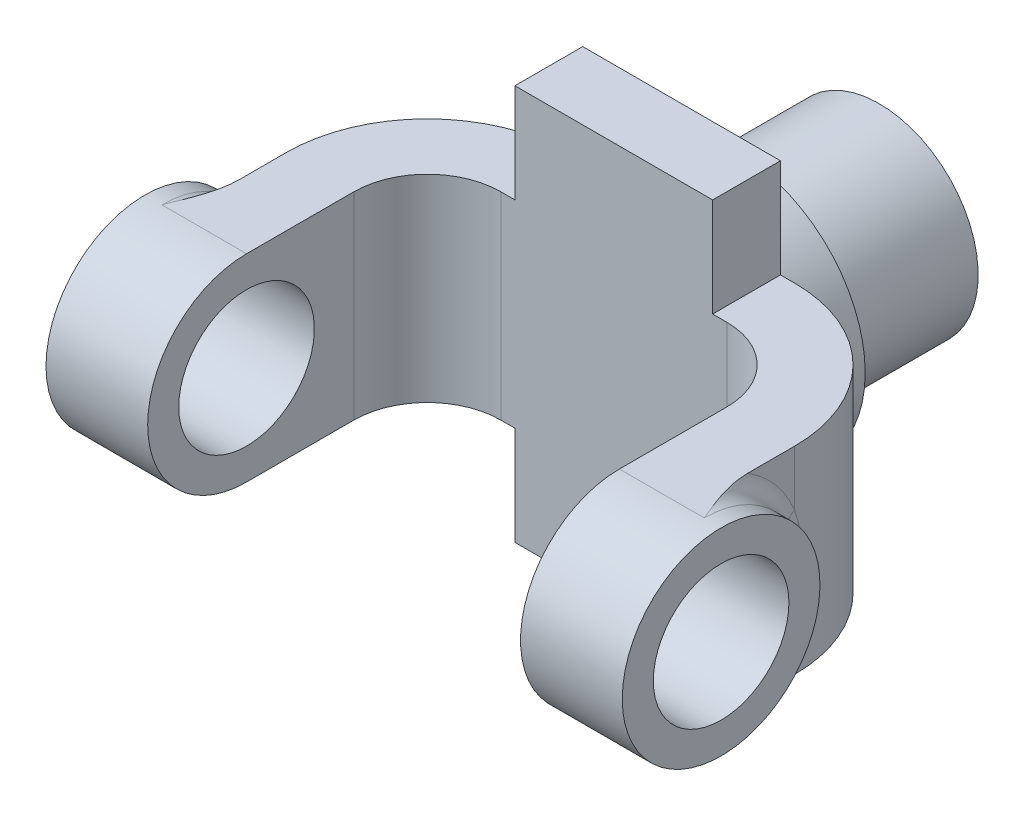
SolidWorks part; units mm, degrees
ref_plane "Спереди" through (0, 0, 0) normal (0, 0, 1) x (1, 0, 0)
ref_plane "Сверху" through (0, 0, 0) normal (0, 1, 0) x (1, 0, 0)
ref_plane "Справа" through (0, 0, 0) normal (1, 0, 0) x (0, 0, -1)
sketch "Эскиз7" plane through (0, 0, 0) normal (0, 0, 1) x (1, 0, 0)
  line L1 (-17.5, -35) -> (17.5, -35)
  line L2 (-17.5, -35) -> (-17.5, 35)
  line L3 (-17.5, 35) -> (17.5, 35)
  line L4 (17.5, -35) -> (17.5, 35)
  line L5 (-17.5, -35) -> (17.5, 35) construction
  line L6 (-17.5, 35) -> (17.5, -35) construction
  point P0 (0, 0)
  dimension "D1" = 70
  dimension "D2" = 35
extrude "Бобышка-Вытянуть4" add sketch "Эскиз7" along normal blind 12
sketch "Эскиз9" plane through (0, 0, 0) normal (0, 0, 1) x (1, 0, 0)
  line L1 (-45, -17.5) -> (45, -17.5)
  line L2 (-45, -17.5) -> (-45, 17.5)
  line L3 (-45, 17.5) -> (45, 17.5)
  line L4 (45, -17.5) -> (45, 17.5)
  line L5 (-45, -17.5) -> (45, 17.5) construction
  line L6 (-45, 17.5) -> (45, -17.5) construction
  point P0 (0, 0)
  dimension "D1" = 35
  dimension "D2" = 90
extrude "Бобышка-Вытянуть5" add sketch "Эскиз9" along normal blind 12
sketch "Эскиз11" plane through (-45, 0, 0) normal (-1, 0, 0) x (0, 0, 1)
  line L0 (12, 17.5) -> (0, 17.5) construction
  line L1 (0, -17.5) -> (44, -17.5)
  line L2 (0, -17.5) -> (0, 17.5)
  line L3 (0, 17.5) -> (44, 17.5)
  arc A0 (44, -17.5) -> (44, 17.5) centre (44, 0) ccw
  point P1 (34.9396, -1.9083)
  point P8 (34.9396, -17.5)
  point P9 (40.9506, 0)
  point P10 (0, 0)
  point P12 (41.1415, 0)
  point P13 (36.2754, -17.5)
  dimension "D1" = 44
ref_plane "Плоскость1" through (-45, 17.5, 12) normal (0, -1, 0) x (-1, 0, 0)
extrude "Бобышка-Вытянуть7" add sketch "Эскиз11" against normal blind 12
sketch "Эскиз16" plane through (-45, 0, 0) normal (-1, 0, 0) x (0, 0, 1)
  circle A0 centre (44, 0) radius 17.5
  arc A1 (44, -17.5) -> (44, 17.5) centre (44, 0) ccw construction
  point P3 (44, 0)
extrude "Бобышка-Вытянуть10" add sketch "Эскиз16" along normal blind 6 contours A0
sketch "Эскиз17" plane through (-51, 0, 0) normal (-1, 0, 0) x (0, 0, 1)
  circle A0 centre (44, 0) radius 12
  dimension "D1" = 24
extrude "Вырез-Вытянуть2" cut sketch "Эскиз17" against normal through all contours A0
mirror "Зеркальное отражение2" about plane through (0, 0, 0) normal (1, 0, 0) of "Бобышка-Вытянуть5", "Бобышка-Вытянуть7"
mirror "Зеркальное отражение3" about plane through (0, 0, 0) normal (1, 0, 0) of "Вырез-Вытянуть2"
mirror "Зеркальное отражение4" about plane through (0, 0, 0) normal (1, 0, 0) of "Бобышка-Вытянуть10", "Бобышка-Вытянуть7"
mirror "Зеркальное отражение5" about plane through (0, 0, 0) normal (1, 0, 0) of "Вырез-Вытянуть2"
fillet "Скругление1" radius 13 2 edges at (-33, 0, 12) (33, 0, 12)
fillet "Скругление2" radius 25 2 edges at (-45, 0, 0) (45, 0, 0)
fillet "Скругление3" radius 3 2 edges at (45, 0, 26.5) (-45, 0, 26.5)
ref_plane "Плоскость2" through (0, 0, -10) normal (0, 0, -1) x (-1, 0, 0)
sketch "Эскиз19" plane through (0, 0, -10) normal (0, 0, -1) x (-1, 0, 0)
  circle A0 centre (0, 0) radius 22.5
  dimension "D1" = 45
extrude "Бобышка-Вытянуть11" add sketch "Эскиз19" against normal up to body separate body contours A0
sketch "Эскиз20" plane through (0, 0, -10) normal (0, 0, -1) x (-1, 0, 0)
  circle A2 centre (0, 0) radius 17.5
  circle A3 centre (0, 0) radius 17.5
  dimension "D1" = 5
extrude "Бобышка-Вытянуть13" add sketch "Эскиз20" along normal blind 25 contours A3
